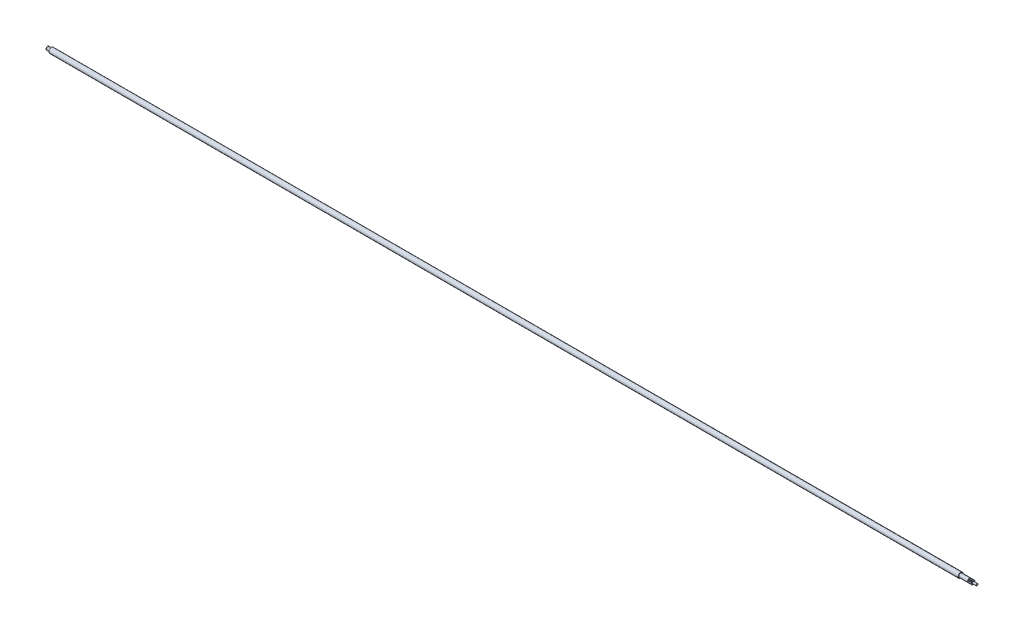
SolidWorks part; units mm, degrees
material "Хромистая нержавеющая сталь"
ref_plane "Спереди" through (0, 0, 0) normal (0, 0, 1) x (1, 0, 0)
ref_plane "Сверху" through (0, 0, 0) normal (0, 1, 0) x (1, 0, 0)
ref_plane "Справа" through (0, 0, 0) normal (1, 0, 0) x (0, 0, -1)
sketch "Эскиз1" plane through (0, 0, 0) normal (0, 0, 1) x (1, 0, 0)
  line L0 (-2813.0019, 5.9419) -> (-2813.0019, 10.9419)
  line L1 (-2813.0019, 10.9419) -> (-2811.3019, 10.9419)
  line L2 (-2811.3019, 10.9419) -> (-2811.3019, 10.7419)
  line L3 (-2811.3019, 10.7419) -> (-2810.1519, 10.7419)
  line L4 (-2810.1519, 10.7419) -> (-2810.1519, 10.9419)
  line L5 (-2810.1519, 10.9419) -> (-2801.0019, 10.9419)
  line L6 (-2801.0019, 10.9419) -> (-2801.0019, 13.9419)
  line L7 (-2801.0019, 13.9419) -> (35.9981, 13.9419)
  line L8 (35.9981, 13.9419) -> (35.9981, 11.9419)
  line L9 (35.9981, 11.9419) -> (74.9981, 11.9419)
  line L10 (74.9981, 11.9419) -> (74.9981, 8.9419)
  line L11 (74.9981, 8.9419) -> (86.9981, 8.9419)
  line L12 (86.9981, 8.9419) -> (86.9981, 5.9419)
  line L13 (86.9981, 5.9419) -> (-2813.0019, 5.9419)
  line L14 (62.9981, 14.6846) -> (62.9981, -1.3142) construction
  dimension "D1" = 1.15
  dimension "D2" = 9.15
  dimension "D3" = 12
  dimension "D4" = 39
  dimension "D5" = 51
  dimension "D6" = 12
  dimension "D7" = 3
  dimension "D8" = 3
  dimension "D9" = 2
  dimension "D10" = 5
  dimension "D11" = 4.8
  dimension "D12" = 5
  dimension "D13" = 2900
revolve "Повернуть1" add sketch "Эскиз1" angle 360 about L13
ref_plane "Плоскость1" through (45.9981, 0, 0) normal (1, 0, 0) x (0, 0, -1)
sketch "Эскиз2" plane through (45.9981, 0, 0) normal (1, 0, 0) x (0, 0, -1)
  circle A0 centre (0, 5.9419) radius 8 construction
  circle A1 centre (0, 5.9419) radius 8
curve "Спираль1" pitch 5 height 290 turns 58
sketch "Эскиз3" plane through (0, 0, 0) normal (0, 0, 1) x (1, 0, 0)
  line L0 (-207.8405, -2.5666) -> (-201.4949, -2.5666) construction
  line L1 (-210.2778, -2.0666) -> (-203.5838, -2.0666) construction
  line L2 (-207.8405, -4.8575) -> (-207.8405, -1.8666) construction
  line L3 (-205.3405, -4.8575) -> (-205.3405, -0.2923) construction
  line L4 (-205.3405, -1.8666) -> (-205.4905, -2.0666)
  line L5 (-205.4905, -2.0666) -> (-205.4905, -2.5666)
  line L6 (-205.4905, -2.5666) -> (-205.1905, -2.5666)
  line L7 (-205.1905, -2.5666) -> (-205.1905, -2.0666)
  line L8 (-205.1905, -2.0666) -> (-205.3405, -1.8666)
  circle A0 centre (-207.8405, -2.5666) radius 1.5875
  point P7 (-207.7498, -2.0666)
  dimension "D1" = 3.175
  dimension "D2" = 0.5
  dimension "D3" = 2.5
  dimension "D4" = 0.2
  dimension "D5" = 0.3
ref_plane "Плоскость2" through (84.9981, 0, 0) normal (1, 0, 0) x (0, 0, -1)
sketch "Эскиз4" plane through (84.9981, 0, 0) normal (1, 0, 0) x (0, 0, -1)
  circle A0 centre (0, 5.9419) radius 6 construction
  circle A1 centre (0, 5.9419) radius 6
curve "Спираль2" pitch 1 height 22 radius 6 centre (84.9981, 5.9419, 0) axis (-1, 0, 0) start towards (0, 0, 1)
sketch "Эскиз5" plane through (0, 0, 0) normal (0, 0, 1) x (1, 0, 0)
  line L0 (76.2561, 0.4419) -> (75.7561, -0.0581)
  line L1 (35.9981, -0.0581) -> (74.9981, -0.0581) construction
  line L2 (75.7561, -0.0581) -> (75.7561, -1.0581)
  line L3 (75.7561, -1.0581) -> (76.7561, -1.0581)
  line L4 (76.7561, -1.0581) -> (76.7561, -0.0581)
  line L5 (76.7561, -0.0581) -> (76.2561, 0.4419)
  line L6 (76.2561, 0.4419) -> (76.2561, -0.2584) construction
  line L7 (75.7561, -0.0581) -> (76.7561, -0.0581) construction
  dimension "D1" = 0.5
  dimension "D2" = 1
  dimension "D3" = 1
sweep "Вырез-По траектории7" cut profiles "Эскиз5" path "Спираль2" align with end faces yes
